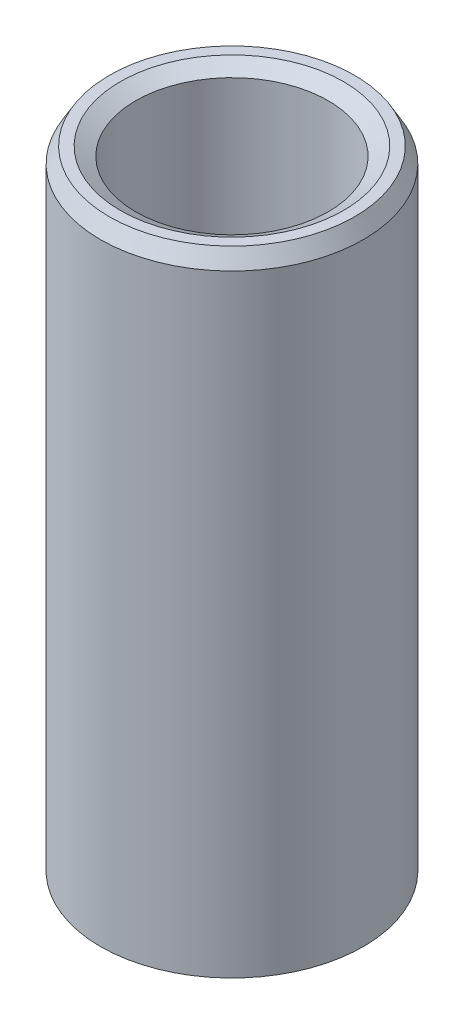
SolidWorks part; units mm, degrees
ref_plane "Front Plane" through (0, 0, 0) normal (0, 0, 1) x (1, 0, 0)
ref_plane "Top Plane" through (0, 0, 0) normal (0, 1, 0) x (1, 0, 0)
ref_plane "Right Plane" through (0, 0, 0) normal (1, 0, 0) x (0, 0, -1)
sketch "Sketch1" plane through (0, 0, 0) normal (0, 1, 0) x (1, 0, 0)
  circle A0 centre (0, 0) radius 27.5
  dimension "SLEEVE_OD" = 55
extrude "Boss-Extrude1" add sketch "Sketch1" along normal blind 133.1563
sketch "Sketch2" plane through (0, 0, 0) normal (0, 1, 0) x (1, 0, 0)
  circle A0 centre (0, 0) radius 20.1442
  dimension "BORE_D" = 40.2885
extrude "Cut-Extrude1" cut sketch "Sketch2" along normal through all
chamfer "Chamfer1" distance 3.2085 angle 30 4 edges at (0, 133.1563, 20.1442) (0, 0, 20.1442) (0, 0, 27.5) (0, 133.1563, 27.5) first distance on face at (0, 133.1563, 20.1442) first distance on face at (0, 0, 20.1442) first distance on face at (0, 133.1563, 27.5)
